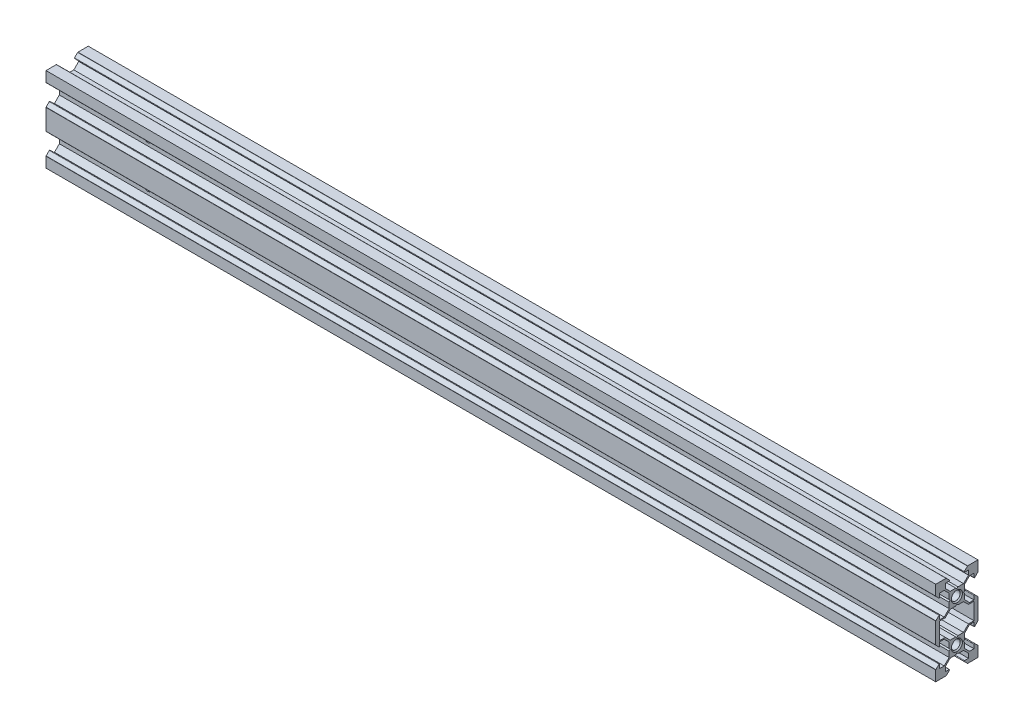
SolidWorks part; units mm, degrees
material "Alloy Steel"
ref_plane "Front Plane" through (0, 0, 0) normal (0, 0, 1) x (1, 0, 0)
ref_plane "Top Plane" through (0, 0, 0) normal (0, 1, 0) x (1, 0, 0)
ref_plane "Right Plane" through (0, 0, 0) normal (1, 0, 0) x (0, 0, -1)
sketch "Sketch2" plane through (0, 0, 0) normal (1, 0, 0) x (0, 0, -1)
  line L0 (0, 2) -> (0, 3) construction
  line L5 (0, 3) -> (-0.5, 3.5)
  line L6 (-0.5, 3.5) -> (-3.01, 3.5)
  line L7 (-3.01, 3.5) -> (-5.2091, 5.6991)
  line L8 (-5.2091, 5.6991) -> (-5.2091, 7.6991)
  line L9 (-5.2091, 7.6991) -> (-3.4791, 7.6991)
  line L10 (-3.4791, 7.6991) -> (-3.4791, 7.8991) construction
  line L11 (-3.4791, 7.8991) -> (-3.3377, 8.0405) construction
  line L12 (-3.3377, 8.0405) -> (-4.7378, 9.4406)
  line L13 (-4.7378, 9.4406) -> (-4.8792, 9.2992) construction
  line L14 (-4.8792, 9.2992) -> (-4.8792, 9.4992) construction
  line L15 (-4.8792, 9.4992) -> (-9.4992, 9.4992)
  line L16 (0, 0) -> (-9.4992, 9.4992) construction
  line L17 (0, 0) -> (-3, 0) construction
  line L18 (-9.4992, 4.8792) -> (-9.4992, 9.4992)
  line L19 (-8.0405, 3.3377) -> (-9.4406, 4.7378)
  line L20 (-7.6991, 5.2091) -> (-7.6991, 3.4791)
  line L21 (-5.6991, 5.2091) -> (-7.6991, 5.2091)
  line L22 (-3.5, 3.01) -> (-5.6991, 5.2091)
  line L23 (-3.5, 0.5) -> (-3.5, 3.01)
  line L24 (-3, 0) -> (-3.5, 0.5)
  line L25 (3, 0) -> (3.5, 0.5)
  line L26 (3.5, 0.5) -> (3.5, 3.01)
  line L27 (3.5, 3.01) -> (5.6991, 5.2091)
  line L28 (5.6991, 5.2091) -> (7.6991, 5.2091)
  line L29 (7.6991, 5.2091) -> (7.6991, 3.4791)
  line L30 (8.0405, 3.3377) -> (9.4406, 4.7378)
  line L31 (9.4992, 4.8792) -> (9.4992, 9.4992)
  line L32 (4.8792, 9.4992) -> (9.4992, 9.4992)
  line L33 (3.3377, 8.0405) -> (4.7378, 9.4406)
  line L34 (5.2091, 7.6991) -> (3.4791, 7.6991)
  line L35 (5.2091, 5.6991) -> (5.2091, 7.6991)
  line L36 (3.01, 3.5) -> (5.2091, 5.6991)
  line L37 (0.5, 3.5) -> (3.01, 3.5)
  line L38 (0, 3) -> (0.5, 3.5)
  line L39 (2, 0) -> (3, 0) construction
  line L40 (7.6991, 3.4791) -> (7.8991, 3.4791) construction
  line L41 (7.8991, 3.4791) -> (8.0405, 3.3377) construction
  line L42 (9.4406, 4.7378) -> (9.2992, 4.8792) construction
  line L43 (9.2992, 4.8792) -> (9.4992, 4.8792) construction
  line L44 (0, 0) -> (9.4992, 9.4992) construction
  line L45 (0, 0) -> (0, 3) construction
  line L46 (0, -3) -> (0.5, -3.5)
  line L47 (0.5, -3.5) -> (3.01, -3.5)
  line L48 (3.01, -3.5) -> (5.2091, -5.6991)
  line L49 (5.2091, -5.6991) -> (7.6991, -5.6991)
  line L50 (7.6991, -5.6991) -> (7.6991, -13.2992)
  line L51 (0, -15.9983) -> (0, -16.8134) construction
  line L52 (7.6991, -13.2992) -> (5.2091, -13.2992)
  line L53 (9.4992, -4.8792) -> (9.4992, -14.1192)
  line L54 (8.0405, -3.3377) -> (9.4406, -4.7378)
  line L55 (7.6991, -5.2091) -> (7.6991, -3.4791)
  line L56 (5.6991, -5.2091) -> (7.6991, -5.2091)
  line L57 (3.5, -3.01) -> (5.6991, -5.2091)
  line L58 (3.5, -0.5) -> (3.5, -3.01)
  line L59 (3, 0) -> (3.5, -0.5)
  line L60 (0, -2) -> (0, -3) construction
  line L61 (-7.6991, -13.2992) -> (-5.2091, -13.2992)
  line L62 (-7.6991, -5.6991) -> (-7.6991, -13.2992)
  line L63 (-5.2091, -5.6991) -> (-7.6991, -5.6991)
  line L65 (0, 0) -> (1.4142, -1.4142) construction
  line L66 (0, 0) -> (3, 0) construction
  line L67 (-3, 0) -> (-3.5, -0.5)
  line L68 (-3.5, -0.5) -> (-3.5, -3.01)
  line L69 (-3.5, -3.01) -> (-5.6991, -5.2091)
  line L70 (-5.6991, -5.2091) -> (-7.6991, -5.2091)
  line L71 (-7.6991, -5.2091) -> (-7.6991, -3.4791)
  line L72 (-8.0405, -3.3377) -> (-9.4406, -4.7378)
  line L73 (-9.4992, -4.8792) -> (-9.4992, -14.1192)
  line L78 (-3.01, -3.5) -> (-5.2091, -5.6991)
  line L79 (-0.5, -3.5) -> (-3.01, -3.5)
  line L80 (0, -3) -> (-0.5, -3.5)
  line L81 (-2, 0) -> (-3, 0) construction
  line L82 (-7.6991, -3.4791) -> (-7.8991, -3.4791) construction
  line L83 (-7.8991, -3.4791) -> (-8.0405, -3.3377) construction
  line L84 (-9.4406, -4.7378) -> (-9.2992, -4.8792) construction
  line L85 (-9.2992, -4.8792) -> (-9.4992, -4.8792) construction
  line L86 (0, 0) -> (-1.4142, -1.4142) construction
  line L87 (0, 0) -> (0, -3) construction
  line L89 (-4.8792, -28.4975) -> (-9.4992, -28.4975)
  line L90 (-3.3377, -27.0389) -> (-4.7378, -28.4389)
  line L91 (-5.2091, -26.6974) -> (-3.4791, -26.6974)
  line L92 (-5.2091, -24.6974) -> (-5.2091, -26.6974)
  line L93 (-9.4992, -23.8775) -> (-9.4992, -28.4975)
  line L94 (-8.0405, -22.336) -> (-9.4406, -23.7361)
  line L95 (-7.6991, -24.2074) -> (-7.6991, -22.4774)
  line L96 (-5.6991, -24.2074) -> (-7.6991, -24.2074)
  line L97 (5.2091, -26.6974) -> (3.4791, -26.6974)
  line L98 (3.3377, -27.0389) -> (4.7378, -28.4389)
  line L99 (4.8792, -28.4975) -> (9.4992, -28.4975)
  line L100 (9.4992, -23.8775) -> (9.4992, -28.4975)
  line L101 (8.0405, -22.336) -> (9.4406, -23.7361)
  line L102 (7.6991, -24.2074) -> (7.6991, -22.4774)
  line L103 (5.6991, -24.2074) -> (7.6991, -24.2074)
  line L104 (5.2091, -24.6974) -> (5.2091, -26.6974)
  line L105 (3.01, -22.4983) -> (5.2091, -24.6974)
  line L106 (3.5, -22.0083) -> (5.6991, -24.2074)
  line L107 (-3.5, -22.0083) -> (-5.6991, -24.2074)
  line L108 (-3.01, -22.4983) -> (-5.2091, -24.6974)
  line L109 (-0.5, -22.4983) -> (-3.01, -22.4983)
  line L110 (0, -21.9983) -> (0.5, -22.4983)
  line L111 (0, -21.9983) -> (-0.5, -22.4983)
  line L112 (0.5, -22.4983) -> (3.01, -22.4983)
  line L113 (3.5, -19.4983) -> (3.5, -22.0083)
  line L114 (-3.5, -19.4983) -> (-3.5, -22.0083)
  line L115 (-3, -18.9983) -> (-3.5, -19.4983)
  line L116 (-3, -18.9983) -> (-3.5, -18.4983)
  line L117 (3, -18.9983) -> (3.5, -19.4983)
  line L118 (3, -18.9983) -> (3.5, -18.4983)
  line L119 (3.5, -18.4983) -> (3.5, -15.9883)
  line L120 (3.01, -15.4983) -> (5.2091, -13.2992)
  line L121 (3.5, -15.9883) -> (5.6991, -13.7892)
  line L122 (5.6991, -13.7892) -> (7.6991, -13.7892)
  line L123 (7.6991, -13.7892) -> (7.6991, -15.5192)
  line L124 (8.0405, -15.6607) -> (9.4406, -14.2606)
  line L128 (-5.6991, -13.7892) -> (-7.6991, -13.7892)
  line L129 (-7.6991, -13.7892) -> (-7.6991, -15.5192)
  line L130 (-8.0405, -15.6607) -> (-9.4406, -14.2606)
  line L134 (-3.01, -15.4983) -> (-5.2091, -13.2992)
  line L135 (-3.5, -15.9883) -> (-5.6991, -13.7892)
  line L136 (-3.5, -18.4983) -> (-3.5, -15.9883)
  line L137 (-0.5, -15.4983) -> (-3.01, -15.4983)
  line L138 (0, -15.9983) -> (-0.5, -15.4983)
  line L139 (0, -15.9983) -> (0.5, -15.4983)
  line L140 (0.5, -15.4983) -> (3.01, -15.4983)
  circle A0 centre (0, 0) radius 2
  arc A1 (-3.3377, 8.0405) -> (-3.4791, 7.6991) centre (-3.4791, 7.8991) cw
  arc A2 (-4.7378, 9.4406) -> (-4.8792, 9.4992) centre (-4.8792, 9.2992) ccw
  arc A3 (-9.4406, 4.7378) -> (-9.4992, 4.8792) centre (-9.2992, 4.8792) cw
  arc A4 (-8.0405, 3.3377) -> (-7.6991, 3.4791) centre (-7.8991, 3.4791) ccw
  arc A5 (8.0405, 3.3377) -> (7.6991, 3.4791) centre (7.8991, 3.4791) cw
  arc A6 (9.4406, 4.7378) -> (9.4992, 4.8792) centre (9.2992, 4.8792) ccw
  arc A7 (4.7378, 9.4406) -> (4.8792, 9.4992) centre (4.8792, 9.2992) cw
  arc A8 (3.3377, 8.0405) -> (3.4791, 7.6991) centre (3.4791, 7.8991) ccw
  arc A11 (9.4406, -4.7378) -> (9.4992, -4.8792) centre (9.2992, -4.8792) cw
  arc A12 (8.0405, -3.3377) -> (7.6991, -3.4791) centre (7.8991, -3.4791) ccw
  arc A13 (-8.0405, -3.3377) -> (-7.6991, -3.4791) centre (-7.8991, -3.4791) cw
  arc A14 (-9.4406, -4.7378) -> (-9.4992, -4.8792) centre (-9.2992, -4.8792) ccw
  arc A17 (-4.7378, -28.4389) -> (-4.8792, -28.4975) centre (-4.8792, -28.2975) cw
  arc A18 (-3.3377, -27.0389) -> (-3.4791, -26.6974) centre (-3.4791, -26.8974) ccw
  arc A19 (-9.4406, -23.7361) -> (-9.4992, -23.8775) centre (-9.2992, -23.8775) ccw
  arc A20 (-8.0405, -22.336) -> (-7.6991, -22.4774) centre (-7.8991, -22.4774) cw
  arc A21 (3.3377, -27.0389) -> (3.4791, -26.6974) centre (3.4791, -26.8974) cw
  arc A22 (4.7378, -28.4389) -> (4.8792, -28.4975) centre (4.8792, -28.2975) ccw
  arc A23 (9.4406, -23.7361) -> (9.4992, -23.8775) centre (9.2992, -23.8775) cw
  arc A24 (8.0405, -22.336) -> (7.6991, -22.4774) centre (7.8991, -22.4774) ccw
  arc A25 (8.0405, -15.6607) -> (7.6991, -15.5192) centre (7.8991, -15.5192) cw
  arc A26 (9.4406, -14.2606) -> (9.4992, -14.1192) centre (9.2992, -14.1192) ccw
  arc A30 (-8.0405, -15.6607) -> (-7.6991, -15.5192) centre (-7.8991, -15.5192) ccw
  arc A31 (-9.4406, -14.2606) -> (-9.4992, -14.1192) centre (-9.2992, -14.1192) cw
  circle A33 centre (0, -18.9983) radius 2
  point P0 (0, 0)
  point P22 (0, 0)
  point P64 (0, 0)
  point P93 (0, 0)
  point P122 (0, 0)
  dimension "D1" = 18.9983
extrude "Main Body" add sketch "Sketch2" along normal blind 200 and the other way blind 200 contours L78 L79 L80 L46 L47 L48 L53 A11 L54 A12 L55 L56 L57 L58 L59 L25 L26 L27 L28 L29 A5 L30 A6 L31 L32 A7 L33 A8 L34 L35 L36 L37 L38 L5 L6 L7 L8 L9 A1 L12 A2 region at (0, 2.9496, -0.5504)
chamfer "Chamfer1" distance 0.5 angle 45 1 edges at (200, 0, -2)
chamfer "Chamfer2" distance 0.5 angle 45 3 edges at (-200, 0, -2) (200, -18.9983, -2) (-200, -18.9983, -2)
sketch "Sketch3" plane through (0, 0, 0) normal (0, 0, 1) x (1, 0, 0)
  line L0 (-200, 0) -> (200, 0) construction
  line L1 (-200, -18.9983) -> (200, -18.9983) construction
  line L2 (-200, -4.8792) -> (-200, -14.1192) construction
  line L3 (-200, -19.4983) -> (-200, -22.0083) construction
  circle A0 centre (-160.25, 0) radius 1.65
  circle A1 centre (-160.25, -18.9983) radius 1.65
  dimension "D1" = 3.3
  dimension "D2" = 3.3
  dimension "D3" = 39.75
  dimension "D4" = 39.75
extrude "Screw Holes" cut sketch "Sketch3" against normal through all both and the other way through all
